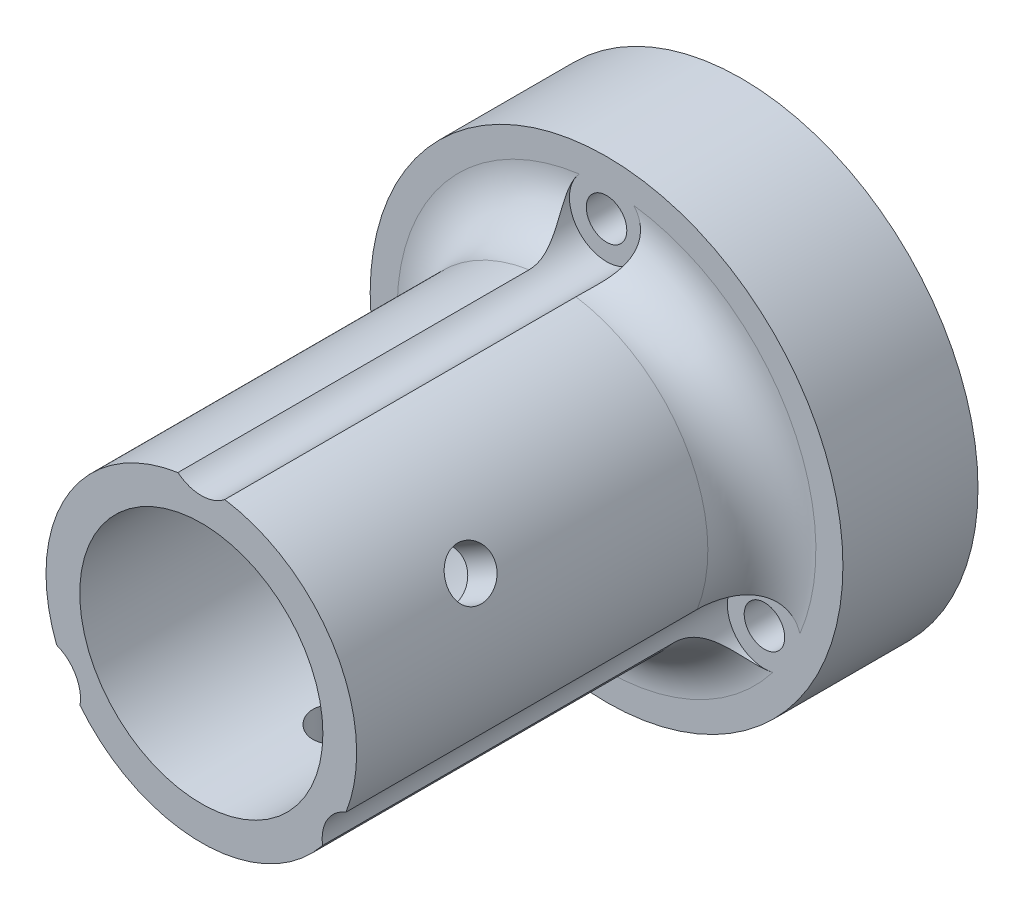
SolidWorks part; units mm, degrees
ref_plane "Front Plane" through (0, 0, 0) normal (0, 0, 1) x (1, 0, 0)
ref_plane "Top Plane" through (0, 0, 0) normal (0, 1, 0) x (1, 0, 0)
ref_plane "Right Plane" through (0, 0, 0) normal (1, 0, 0) x (0, 0, -1)
sketch "Sketch1" plane through (0, 0, 0) normal (0, 0, 1) x (1, 0, 0)
  circle A0 centre (0, 0) radius 17.5
  circle A1 centre (0, 0) radius 13.5 construction
  circle A2 centre (0, 0) radius 10
  circle A3 centre (0, 13.5) radius 1.5
  circle A4 centre (11.6913, -6.75) radius 1.5
  circle A5 centre (-11.6913, -6.75) radius 1.5
  point P13 (0, 0)
  dimension "D1" = 20
  dimension "D2" = 35
  dimension "D3" = 27
  dimension "D4" = 3
  dimension "D5" = 3
extrude "Boss-Extrude1" add sketch "Sketch1" along normal blind 10 contours A0 A5 A4 A3 A2 | A2 region at (-17.005, 0, 0)
sketch "Sketch2" plane through (0, 0, 10) normal (0, 0, 1) x (1, 0, 0)
  circle A0 centre (0, 0) radius 9
  arc A1 (10.712, -4.1837) -> (1.7328, 11.3687) centre (0, 0) ccw
  arc A2 (-1.7328, 11.3687) -> (1.7328, 11.3687) centre (0, 13.5) ccw
  arc A3 (-8.9792, -7.185) -> (-10.712, -4.1837) centre (-11.6913, -6.75) ccw
  arc A4 (10.712, -4.1837) -> (8.9792, -7.185) centre (11.6913, -6.75) ccw
  arc A5 (-8.9792, -7.185) -> (8.9792, -7.185) centre (0, 0) ccw
  arc A6 (-1.7328, 11.3687) -> (-10.712, -4.1837) centre (0, 0) ccw
  dimension "D1" = 18
  dimension "D2" = 23
extrude "Boss-Extrude2" add sketch "Sketch2" along normal blind 30
extrude "Cut-Extrude1" cut sketch "Sketch2<2>" against normal through all contours A0 region at (0, 0, 10)
sketch "Sketch2<2>" plane through (0, 0, 10) normal (0, 0, 1) x (1, 0, 0) same geometry as "Sketch2"
fillet "Fillet1" radius 4 3 edges at (-9.9593, 5.75, 10) (9.9593, 5.75, 10) (0, -11.5, 10)
ref_plane "Plane1" through (0, 0, 30) normal (0, 0, 1) x (1, 0, 0)
sketch "Sketch4" plane through (0, 0, 30) normal (0, 0, 1) x (1, 0, 0)
  line L0 (0, 0) -> (0, -21.6442) construction
  line L1 (0, 0) -> (-25.7086, 14.8428) construction
  line L2 (0, 0) -> (28.0865, 16.2158) construction
  line L3 (-6.6758, 3.8543) -> (-7.5508, 2.3388)
  line L4 (-7.5508, 2.3388) -> (-17.7335, 8.2177)
  line L5 (-17.7335, 8.2177) -> (-16.8585, 9.7333)
  line L6 (-16.8585, 9.7333) -> (-6.6758, 3.8543)
  line L7 (16.8585, 9.7333) -> (6.6758, 3.8543)
  line L8 (6.6758, 3.8543) -> (5.8008, 5.3698)
  line L9 (5.8008, 5.3698) -> (15.9835, 11.2488)
  line L10 (15.9835, 11.2488) -> (16.8585, 9.7333)
  line L11 (0, -19.4665) -> (0, -7.7086)
  line L12 (0, -7.7086) -> (1.75, -7.7086)
  line L13 (1.75, -7.7086) -> (1.75, -19.4665)
  line L14 (1.75, -19.4665) -> (0, -19.4665)
  point P19 (0, 0)
  dimension "D1" = 120
  dimension "D2" = 120
  dimension "D4" = 1.75
  dimension "D3" = 3
revolve "Cut-Revolve1" cut sketch "Sketch4" angle 360 about L1 region at (-12.2047, 6.036, 30)
revolve "Cut-Revolve2" cut sketch "Sketch4<3>" angle 360 about L2 region at (11.3297, 7.5516, 30)
sketch "Sketch4<3>" plane through (0, 0, 30) normal (0, 0, 1) x (1, 0, 0) same geometry as "Sketch4"
revolve "Cut-Revolve3" cut sketch "Sketch4<4>" angle 360 about L0 region at (0.875, -13.5876, 30)
sketch "Sketch4<4>" plane through (0, 0, 30) normal (0, 0, 1) x (1, 0, 0) same geometry as "Sketch4"
equation "\"fuse_diam\"= 0.07"
equation "\"fuse_rad\"= 0.035"
equation "\"battery_length\"= 0.076"
equation "\"battery_width\"= 0.034"
equation "\"battery_height\"= 0.051"
equation "\"bat_bay_length\"= 0.096"
equation "\"wing_shelf\"= 0.0175"
equation "\"shell\"= 0.002"
equation "\"chord_length\"= 0.09"
equation "\"tail_length\"= 0.26598000000000005"
equation "\"tail_diam\"= 0.035"
equation "\"connector\"= 0.06649500000000001"
equation "\"D2@Sketch1\"=\"fuse_rad\""
equation "\"D3@Sketch1\"=\"fuse_diam\"/2 - 0.008"
